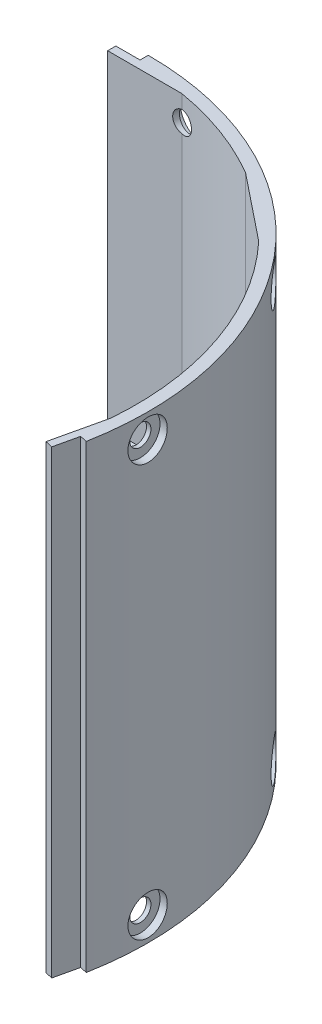
SolidWorks part; units mm, degrees
ref_plane "Спереди" through (0, 0, 0) normal (0, 0, 1) x (1, 0, 0)
ref_plane "Сверху" through (0, 0, 0) normal (0, 1, 0) x (1, 0, 0)
ref_plane "Справа" through (0, 0, 0) normal (1, 0, 0) x (0, 0, -1)
sketch "Эскиз2" plane through (0, 0, 0) normal (0, 1, 0) x (1, 0, 0)
  line L0 (0, -1000) -> (0, 49000) construction
  line L1 (-8.2529, 48.3) -> (8.2529, 48.3) construction
  line L2 (35.7629, 33.4965) -> (24.8621, 42.2241) construction
  line L3 (48.839, -3.9694) -> (45.736, -17.5845) construction
  line L4 (-4, 48.3) -> (8.2529, 48.3)
  line L5 (35.7629, 33.4965) -> (24.8621, 42.2241)
  line L6 (48.839, -3.9694) -> (45.736, -17.5845) construction
  line L7 (-4, 48.3) -> (-4, 49.65)
  line L8 (-4, 49.65) -> (0, 49.65)
  line L10 (-8.2529, 48.3) -> (-4, 48.3) construction
  line L12 (0, 0) -> (47.2875, -10.7769) construction
  line L13 (50.1312, -9.3737) -> (48.9507, -9.1047)
  line L14 (48.9507, -9.1047) -> (48.0618, -13.0047)
  line L15 (48.0618, -13.0047) -> (46.8431, -12.7269)
  line L16 (47.2875, -10.7769) -> (49.725, -11.3324) construction
  line L17 (46.8431, -12.7269) -> (48.839, -3.9694)
  line L19 (0, 49.65) -> (0, 51)
  line L20 (0, 48.3) -> (0, 49.65) construction
  circle A0 centre (0, 0) radius 51 construction
  arc A1 (50.1312, -9.3737) -> (0, 51) centre (0, 0) ccw
  circle A2 centre (0, 0) radius 51 construction
  arc A3 (48.839, -3.9694) -> (35.7629, 33.4965) centre (0, 0) ccw construction
  arc A4 (0, 51) -> (0, -51) centre (0, 0) ccw construction
  arc A5 (48.839, -3.9694) -> (35.7629, 33.4965) centre (0, 0) ccw
  arc A6 (8.2529, 48.3) -> (24.8621, 42.2241) centre (0, 0) cw
  arc A7 (0, -51) -> (49.725, -11.3324) centre (0, 0) ccw construction
  arc A8 (49.725, -11.3324) -> (50.1312, -9.3737) centre (0, 0) ccw construction
  point P25 (48.5063, -11.0547)
  dimension "D1" = 4
extrude "Бобышка-Вытянуть2" add sketch "Эскиз2" along normal up to surface (76 mm away)
ref_plane "Плоскость4" through (12.7171, 0, -36.1271) normal (-0.332, 0, 0.9433) x (0.9433, 0, 0.332)
sketch "Эскиз7" plane through (12.7171, 0, -36.1271) normal (-0.332, 0, 0.9433) x (0.9433, 0, 0.332)
  line L5 (-8.2529, 17) -> (5.2529, 17) construction
  line L6 (-8.2529, 17) -> (5.2529, 17) construction
  line L7 (8.2529, 14) -> (5.2529, 17) construction
  line L8 (8.2529, 14) -> (5.2529, 17)
  line L9 (-8.2529, 0) -> (8.2529, 0) construction
  line L16 (-8.2529, 0) -> (8.2529, 0)
  line L17 (-8.2529, 76) -> (-8.2529, 0) construction
  line L18 (-8.2529, 17) -> (-8.2529, 0) construction
  line L19 (8.7529, 14.2071) -> (8.7529, 0)
  line L20 (8.7529, 14.2071) -> (5.46, 17.5)
  line L21 (8.2529, 14) -> (8.2529, 0) construction
  line L22 (8.2529, 14) -> (8.2529, 0) construction
  line L23 (-8.7529, 17.5) -> (5.46, 17.5)
  line L24 (-8.7529, 17.5) -> (-8.7529, 0)
  line L25 (-8.7529, 0) -> (-8.2529, 0)
  line L26 (8.2529, 0) -> (8.7529, 0)
  dimension "D1" = 0.5
extrude "Вырез-Вытянуть3" cut sketch "Эскиз7" against normal through all contours L16 L26 L19 L20 L23 L24 L25 region at (12.587, 8.6121, -36.1729)
sketch "Эскиз9" plane through (0, 0, -48.3) normal (0, 0, 1) x (1, 0, 0)
  line L4 (8.7529, 0) -> (8.7529, 17.5)
  line L6 (-4, 76) -> (-4, 0) construction
  line L7 (-4, 19.5) -> (-4, 0)
  line L8 (-4, 76) -> (-4, 19.5) construction
  line L9 (-4, 19.5) -> (-6.5, 17) construction
  line L10 (-8.2529, 0) -> (-4, 0) construction
  line L11 (8.7529, 17.5) -> (6.7071, 17.5)
  line L12 (6.7071, 17.5) -> (3.7071, 20.5)
  line L13 (3.7071, 20.5) -> (-3.7071, 20.5)
  line L14 (-8.2529, 0) -> (8.2529, 0)
  line L15 (8.2529, 0) -> (8.2529, 17)
  line L24 (8.2529, 17) -> (6.5, 17)
  line L25 (6.5, 17) -> (3.5, 20)
  line L26 (3.5, 20) -> (-3.5, 20)
  line L28 (-3.7071, 20.5) -> (-4, 20.2071)
  line L29 (-3.5, 20) -> (-6.5, 17)
  line L30 (-6.5, 17) -> (-8.2529, 17)
  line L31 (-8.2529, 17) -> (-8.2529, 0)
  line L32 (-4, 0) -> (8.2529, 0)
  line L33 (8.2529, 0) -> (8.2529, 17) construction
  line L34 (8.2529, 17) -> (6.5, 17) construction
  line L35 (6.5, 17) -> (3.5, 20) construction
  line L36 (3.5, 20) -> (-3.5, 20) construction
  line L37 (-3.5, 20) -> (-4, 19.5)
  line L38 (-6.5, 17) -> (-8.2529, 17) construction
  line L39 (-8.2529, 17) -> (-8.2529, 0) construction
  line L40 (-4, 19.5) -> (-4, 20.2071)
  line L41 (-4, 20.2071) -> (-4.3536, 19.8536) construction
  line L42 (-3.7071, 20.5) -> (-4.3536, 19.8536) construction
  line L43 (8.7529, 0) -> (8.2529, 0)
  line M9 (-8.2529, 0) -> (8.2529, 0)
  line M10 (8.2529, 0) -> (8.2529, 17)
  line M11 (8.2529, 17) -> (6.5, 17)
  line M12 (6.5, 17) -> (3.5, 20)
  line M13 (3.5, 20) -> (-3.5, 20)
  line M14 (-3.5, 20) -> (-6.5, 17)
  dimension "D1" = 0
  dimension "D2" = 0.5
extrude "Вырез-Вытянуть4" cut sketch "Эскиз9" against normal through all contours L7 M14 M9 M10 M11 M12 M13 | L43 L4 L11 L12 L13 L28 L40 M14 M13 M12 M11 M10 region at (8.5029, 0.2414, -48.3) region at (1.9477, 9.6325, -48.3)
sketch "Эскиз10" plane through (0, 12, 0) normal (0, 1, 0) x (1, 0, 0)
  line L0 (-4, 48.3) -> (8.2529, 48.3) construction
  line L1 (-4, 48.3) -> (8.2529, 48.3)
  line L2 (23.8222, 42.8194) -> (20.9924, 43.8155) construction
  line L3 (8.2529, 48.3) -> (20.9924, 43.8155) construction
  line L4 (23.8222, 42.8194) -> (20.9924, 43.8155)
  line L5 (8.2529, 48.3) -> (20.9924, 43.8155)
  line L7 (23.4097, 41.9045) -> (20.6603, 42.8723)
  line L8 (8.082, 47.3) -> (20.6603, 42.8723)
  line L9 (-4, 47.3) -> (8.082, 47.3)
  line L10 (-4, 47.3) -> (-4, 48.3)
  line L11 (24.3547, 41.3624) -> (24.8621, 42.2241) construction
  line L12 (24.3547, 41.3624) -> (26.3116, 41.0636)
  line L13 (24.8621, 42.2241) -> (35.7629, 33.4965) construction
  line L14 (26.3116, 41.0636) -> (24.8621, 42.2241) construction
  line L15 (26.3116, 41.0636) -> (24.8621, 42.2241) construction
  line L16 (26.3116, 41.0636) -> (24.8621, 42.2241)
  arc A0 (24.8621, 42.2241) -> (8.2529, 48.3) centre (0, 0) ccw construction
  arc A1 (24.8621, 42.2241) -> (23.8222, 42.8194) centre (0, 0) ccw
  arc A2 (23.8222, 42.8194) -> (8.2529, 48.3) centre (0, 0) ccw construction
  arc A3 (24.3547, 41.3624) -> (23.4097, 41.9045) centre (0, 0) ccw
  dimension "D2" = 30
  dimension "D1" = 1
extrude "Бобышка-Вытянуть7" add sketch "Эскиз10" along normal blind 10
sketch "Эскиз13" plane through (0, 22, 0) normal (0, 1, 0) x (1, 0, 0)
  line L0 (23.8222, 42.8194) -> (8.2529, 48.3) construction
  line L1 (23.8222, 42.8194) -> (8.2529, 48.3)
  arc A0 (24.8621, 42.2241) -> (8.2529, 48.3) centre (0, 0) ccw construction
  arc A1 (24.8621, 42.2241) -> (8.2529, 48.3) centre (0, 0) ccw
  line M2 (23.8222, 42.8194) -> (8.2529, 48.3)
extrude "Бобышка-Вытянуть8" add sketch "Эскиз13" against normal up to surface (4.5 mm away) contours A1 M2 region at (16.1306, 22, -45.824) up to face at (13.0597, 17.5, -47.6707)
sketch "Эскиз14" plane through (0, 17.5, 0) normal (0, -1, 0) x (1, 0, 0)
  line L0 (21.3189, -44.1192) -> (21.1877, -43.7468)
  line L1 (21.1877, -43.7468) -> (8.2529, -48.3) construction
  line L4 (21.9869, -46.0171) -> (21.3189, -44.1192)
  line L5 (23.8222, -42.8194) -> (8.2529, -48.3)
  line L6 (8.2529, -48.3) -> (6.7071, -48.3)
  line L7 (6.7071, -48.3) -> (6.7071, -50.557)
  line L8 (21.9869, -46.0171) -> (21.3189, -44.1192)
  line L9 (23.8222, -42.8194) -> (21.1877, -43.7468)
  line L10 (8.2529, -48.3) -> (6.7071, -48.3) construction
  line L11 (6.7071, -48.3) -> (6.7071, -50.557) construction
  arc A2 (6.7071, -50.557) -> (21.9869, -46.0171) centre (0, 0) ccw
  arc A3 (21.3189, -44.1192) -> (23.8222, -42.8194) centre (0, 0) ccw
  arc A4 (6.7071, -50.557) -> (21.9869, -46.0171) centre (0, 0) ccw construction
  arc A5 (21.3189, -44.1192) -> (23.8222, -42.8194) centre (0, 0) ccw
  dimension "D1" = 0
extrude "Бобышка-Вытянуть9" add sketch "Эскиз14" along normal up to surface contours A5 L9 L0 up to face at (23.2708, 15.6229, -44.011)
chamfer "Фаска1" distance 1 angle 45 4 edges at (2.041, 22, -47.3) (15.7459, 22, -44.6022) (23.8837, 22, -41.6361) (25.3331, 22, -41.213)
ref_plane "Плоскость5" through (51, 0, 0) normal (1, 0, 0) x (0, 0, -1)
sketch "Эскиз15" plane through (51, 0, 0) normal (1, 0, 0) x (0, 0, -1)
  line L0 (0, -1000) -> (0, 49000) construction
  circle A0 centre (0, 4) radius 3.25
  point P5 (0, 6.0834)
  dimension "D1" = 6.5
  dimension "D2" = 4
extrude "Вырез-Вытянуть5" cut sketch "Эскиз15" against normal blind 1.3
sketch "Эскиз16" plane through (49.7, 0, 0) normal (1, 0, 0) x (0, 0, -1)
  circle A0 centre (0, 4) radius 3.25 construction
  circle A1 centre (0, 4) radius 3.25 construction
  circle A2 centre (0, 4) radius 1.75
  dimension "D1" = 3.5
extrude "Вырез-Вытянуть6" cut sketch "Эскиз16" against normal through all
pattern_circular "Круговой массив3" count 3 every 20 about axis through (0, 0, 0) along (0, 1, 0) skipping 1 of "Вырез-Вытянуть5", "Вырез-Вытянуть6"
sketch "Эскиз17" plane through (51, 0, 0) normal (1, 0, 0) x (0, 0, -1)
  line L0 (0, -1000) -> (0, 49000) construction
  line L1 (51, 76) -> (-9.3737, 76) construction
  circle A0 centre (0, 72) radius 3.25
  circle A1 centre (0, 4) radius 3.25 construction
  dimension "D1" = 4
extrude "Вырез-Вытянуть7" cut sketch "Эскиз17" against normal blind 1.3
sketch "Эскиз18" plane through (49.7, 0, 0) normal (1, 0, 0) x (0, 0, -1)
  circle A0 centre (0, 72) radius 3.25 construction
  circle A1 centre (0, 72) radius 3.25 construction
  circle A2 centre (0, 72) radius 1.75
  circle A3 centre (0, 4) radius 1.75 construction
extrude "Вырез-Вытянуть8" cut sketch "Эскиз18" against normal through all
pattern_circular "Круговой массив5" count 5 every 20 about axis through (0, 76, 0) along (0, 1, 0) skipping 1, 3 of "Вырез-Вытянуть8", "Вырез-Вытянуть7"
